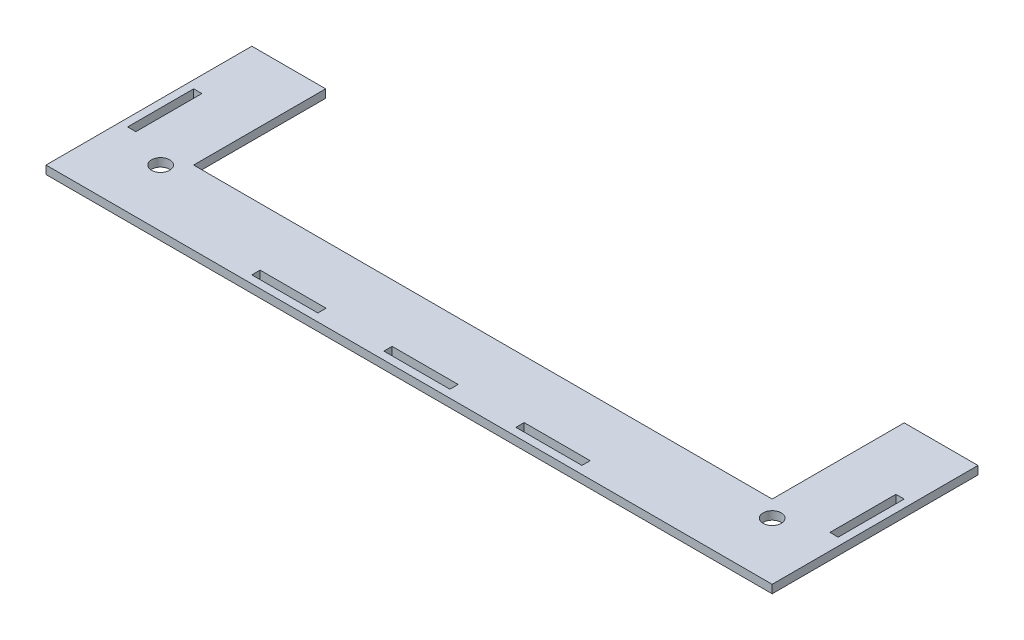
SolidWorks part; units mm, degrees
ref_plane "Front Plane" through (0, 0, 0) normal (0, 0, 1) x (1, 0, 0)
ref_plane "Top Plane" through (0, 0, 0) normal (0, 1, 0) x (1, 0, 0)
ref_plane "Right Plane" through (0, 0, 0) normal (1, 0, 0) x (0, 0, -1)
sketch "Sketch1" plane through (0, 0, 0) normal (0, 1, 0) x (1, 0, 0)
  line L0 (-136.7, 63.5) -> (-111.3, 63.5)
  line L1 (-111.3, 63.5) -> (-111.3, 12.7)
  line L2 (-111.3, 12.7) -> (111.3, 12.7)
  line L3 (111.3, 12.7) -> (111.3, 63.5)
  line L4 (111.3, 63.5) -> (136.7, 63.5)
  line L5 (136.7, 63.5) -> (136.7, -12.7)
  line L6 (136.7, -12.7) -> (-136.7, -12.7)
  line L7 (-136.7, -12.7) -> (-136.7, 63.5)
  line L8 (0, 12.7) -> (0, -12.7) construction
  line L9 (-111.3, 12.7) -> (-111.3, 6.35) construction
  line L10 (-111.3, 6.35) -> (-117.65, 6.35) construction
  line L11 (111.3, 12.7) -> (111.3, 6.35) construction
  line L12 (111.3, 6.35) -> (117.65, 6.35) construction
  line L13 (-38.1, -9.525) -> (-12.7, -9.525) construction
  line L14 (-12.7, -12.7) -> (12.7, -12.7)
  line L15 (-12.7, -12.7) -> (-12.7, -9.525)
  line L16 (-12.7, -9.525) -> (12.7, -9.525)
  line L17 (12.7, -12.7) -> (12.7, -9.525)
  line L18 (38.1, -12.7) -> (63.5, -12.7)
  line L19 (38.1, -12.7) -> (38.1, -9.525)
  line L20 (38.1, -9.525) -> (63.5, -9.525)
  line L21 (63.5, -12.7) -> (63.5, -9.525)
  line L22 (-63.5, -12.7) -> (-38.1, -12.7)
  line L23 (-63.5, -12.7) -> (-63.5, -9.525)
  line L24 (-63.5, -9.525) -> (-38.1, -9.525)
  line L25 (-38.1, -12.7) -> (-38.1, -9.525)
  line L26 (12.7, -9.525) -> (38.1, -9.525) construction
  line L27 (-133.525, 12.7) -> (-133.525, -12.7) construction
  line L28 (-136.7, 12.7) -> (-133.525, 12.7)
  line L29 (-136.7, 12.7) -> (-136.7, 38.1)
  line L30 (-136.7, 38.1) -> (-133.525, 38.1)
  line L31 (-133.525, 12.7) -> (-133.525, 38.1)
  line L32 (136.7, 12.7) -> (133.525, 12.7)
  line L33 (136.7, 12.7) -> (136.7, 38.1)
  line L34 (136.7, 38.1) -> (133.525, 38.1)
  line L35 (133.525, 12.7) -> (133.525, 38.1)
  line L36 (-136.7, 63.5) -> (-139.7, 63.5)
  line L37 (-139.7, 63.5) -> (-139.7, -15.7)
  line L38 (-139.7, -15.7) -> (139.7, -15.7)
  line L39 (139.7, -15.7) -> (139.7, 63.5)
  line L40 (139.7, 63.5) -> (136.7, 63.5)
  line L41 (-136.7, -12.7) -> (-136.7, -15.7) construction
  circle A0 centre (-117.65, 6.35) radius 3.5
  circle A1 centre (117.65, 6.35) radius 3.5
  point P10 (0, 12.7)
  point P11 (0, -12.7)
  point P14 (0, 0)
  point P32 (0, -9.525)
  dimension "D5" = 7
  dimension "D1" = 273.4
  dimension "D2" = 76.2
  dimension "D3" = 25.4
  dimension "D4" = 25.4
  dimension "D6" = 6.35
  dimension "D7" = 25.4
  dimension "D8" = 3.175
  dimension "D9" = 25.4
  dimension "D10" = 3.175
  dimension "D11" = 3
extrude "Boss-Extrude1" add sketch "Sketch1" along normal blind 3.175 contours L25 L6 L15 L16 L17 L19 L20 L21 L5 L4 L3 L2 L1 L0 L7 L23 L24 A1 A0 | L39 L40 L5 L6 L7 L36 L37 L38 region at (0, 0, -10.6609) region at (-139.6041, 0, -50.8)
